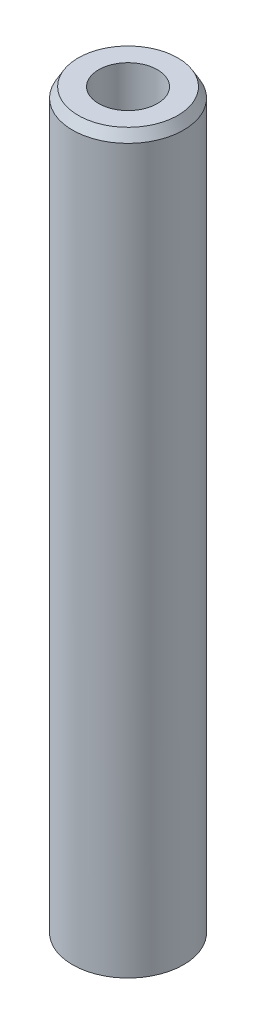
SolidWorks part; units mm, degrees
ref_plane "Front Plane" through (0, 0, 0) normal (0, 0, 1) x (1, 0, 0)
ref_plane "Top Plane" through (0, 0, 0) normal (0, 1, 0) x (1, 0, 0)
ref_plane "Right Plane" through (0, 0, 0) normal (1, 0, 0) x (0, 0, -1)
sketch "Sketch1" plane through (0, 0, 0) normal (0, 1, 0) x (1, 0, 0)
  circle A0 centre (0, 0) radius 5
  dimension "SHAFT_OD" = 10
extrude "Boss-Extrude1" add sketch "Sketch1" along normal blind 66.4862
sketch "Sketch2" plane through (0, 0, 0) normal (0, 1, 0) x (1, 0, 0)
  circle A0 centre (0, 0) radius 2.6439
  dimension "BORE_D" = 5.2878
extrude "Cut-Extrude1" cut sketch "Sketch2" along normal through all
chamfer "Chamfer1" distance 0.8908 angle 30 2 edges at (0, 66.4862, 5) (0, 0, 5) first distance on face at (0, 66.4862, 5) first distance on face at (0, 0, 2.6439)
